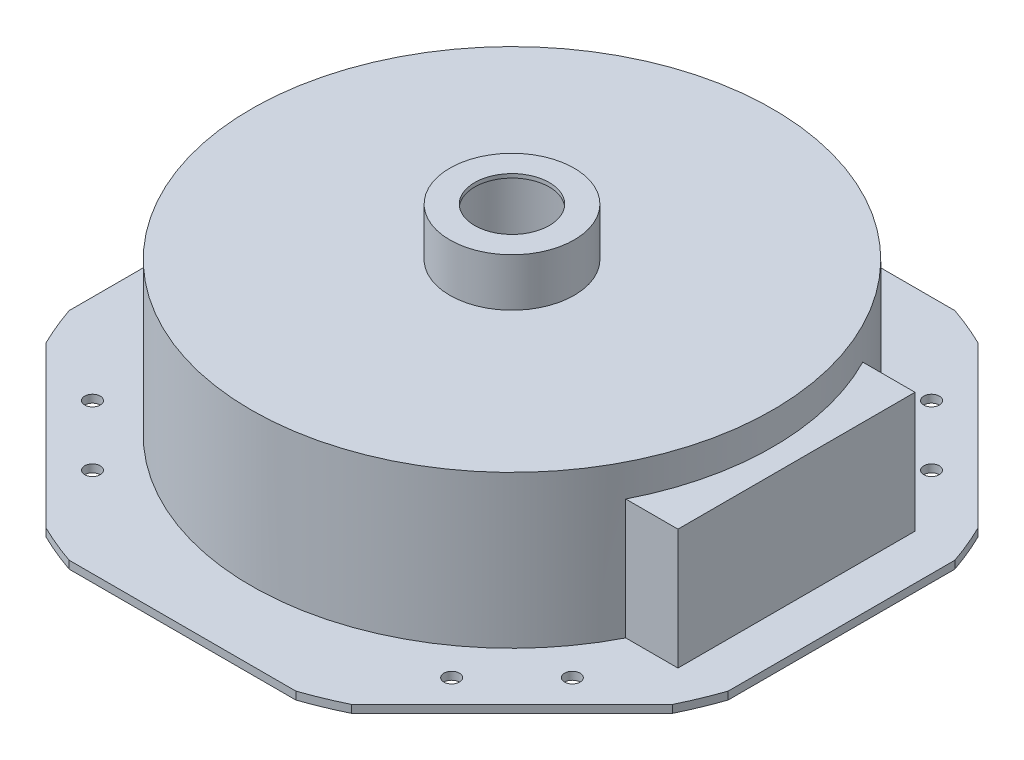
SolidWorks part; units mm, degrees
ref_plane "前视基准面" through (0, 0, 0) normal (0, 0, 1) x (1, 0, 0)
ref_plane "上视基准面" through (0, 0, 0) normal (0, 1, 0) x (1, 0, 0)
ref_plane "右视基准面" through (0, 0, 0) normal (1, 0, 0) x (0, 0, -1)
other "Configuration Table"
sketch "草图1" plane through (0, 0, 0) normal (0, 1, 0) x (1, 0, 0)
  line L1 (-175.6058, 423.95) -> (-423.95, 175.6058)
  line L2 (-423.95, 175.6058) -> (-423.95, -175.6058)
  line L3 (-423.95, -175.6058) -> (-175.6058, -423.95)
  line L4 (-175.6058, -423.95) -> (175.6058, -423.95)
  line L5 (175.6058, -423.95) -> (423.95, -175.6058)
  line L6 (423.95, -175.6058) -> (423.95, 175.6058)
  line L7 (423.95, 175.6058) -> (175.6058, 423.95)
  line L8 (175.6058, 423.95) -> (-175.6058, 423.95)
  circle A0 centre (0, 0) radius 423.95 construction
  circle A1 centre (0, 0) radius 448.35
  dimension "D2" = 896.7
  dimension "D1" = 847.9
extrude "凸台-拉伸1" add sketch "草图1" along normal blind 10 contours L4 A1 L5 L6 L7 L8 L1 L2 L3 region at (0, 0, 0)
sketch "草图2" plane through (0, 10, 0) normal (0, 1, 0) x (1, 0, 0)
  circle A0 centre (0, 0) radius 335.5
  dimension "D1" = 671
extrude "凸台-拉伸2" add sketch "草图2" along normal blind 196 separate body
sketch "草图3" plane through (0, 10, 0) normal (0, 1, 0) x (1, 0, 0)
  line L0 (0, 0) -> (423.95, 0) construction
  line L1 (423.95, -145.8908) -> (423.95, 145.8908) construction
  line L2 (366, 152.5) -> (366, -152.5)
  line L3 (366, 152.5) -> (298.8377, 152.5)
  line L4 (366, -152.5) -> (298.8377, -152.5)
  circle A0 centre (0, 0) radius 335.5 construction
  arc A1 (298.8377, -152.5) -> (298.8377, 152.5) centre (0, 0) ccw
  point P10 (366, 0)
  dimension "D1" = 305
  dimension "D2" = 366
extrude "凸台-拉伸4" add sketch "草图3" along normal blind 154.8 separate body
combine bodies "组合1" operation type add bodies to combine 107 109
shell "抽壳4" thickness 5 removed face at (173.8344, 10, 0)
sketch "草图5" plane through (0, 10, 0) normal (0, -1, 0) x (1, 0, 0)
  line L0 (361, -147.5) -> (295.76, -147.5) construction
  line L1 (361, 147.5) -> (361, -147.5) construction
  line L2 (295.76, 147.5) -> (361, 147.5) construction
  line L3 (361, -147.5) -> (295.76, -147.5) construction
  line L4 (361, 147.5) -> (361, -147.5) construction
  line L5 (295.76, 147.5) -> (361, 147.5) construction
  line L6 (356, -142.5) -> (292.65, -142.5)
  line L7 (356, 142.5) -> (356, -142.5)
  line L8 (292.65, 142.5) -> (356, 142.5)
  circle A0 centre (0, 0) radius 330.5 construction
  arc A1 (295.76, 147.5) -> (295.76, -147.5) centre (0, 0) ccw construction
  arc A2 (292.65, 142.5) -> (292.65, -142.5) centre (0, 0) ccw
  dimension "D1" = 5
extrude "切除-拉伸2" cut sketch "草图5" along normal blind 196
combine bodies "组合2" operation type add bodies to combine 110 112
sketch "草图6" plane through (0, 201, 0) normal (0, -1, 0) x (1, 0, 0)
  circle A0 centre (0, 0) radius 80
  dimension "D1" = 160
extrude "凸台-拉伸6" add sketch "草图6" against normal offset from surface (66.8 mm away) 267.8 up to face at (0, 0, 0)
extrude "凸台-拉伸7" add sketch "草图6<2>" along normal offset from surface (123.6 mm away) 77.4 up to face at (0, 0, 0)
sketch "草图6<2>" plane through (0, 201, 0) normal (0, -1, 0) x (1, 0, 0) same geometry as "草图6"
sketch "草图7" plane through (0, 77.4, 0) normal (0, -1, 0) x (1, 0, 0)
  circle A2 centre (0, 0) radius 75
  circle A3 centre (0, 0) radius 75
  dimension "D1" = 5
extrude "切除-拉伸3" cut sketch "草图7" against normal offset from surface (185.4 mm away) 5 up to face at (0, 267.8, 80)
sketch "草图9" plane through (0, 0, 0) normal (0, -1, 0) x (1, 0, 0)
  line L0 (-231.0613, 308.7016) -> (-308.7016, 231.0613) construction
  line L1 (-402.9383, 196.6176) -> (-196.6176, 402.9383) construction
  line L2 (-269.8814, 269.8814) -> (-299.7779, 299.7779) construction
  circle A0 centre (-308.7016, 231.0613) radius 10
  circle A1 centre (-231.0613, 308.7016) radius 10
  dimension "D1" = 20
  dimension "D2" = 42.28
  dimension "D3" = 109.8
extrude "切除-拉伸11" cut sketch "草图9" against normal blind 25
pattern_circular "阵列(圆周)1" count 4 over 360 about axis through (0, 206, 0) along (0, -1, 0) of "切除-拉伸11" reverse direction yes
sketch "草图10" plane through (0, 0, 0) normal (0, 0, 1) x (1, 0, 0)
  line L0 (-80, 82.4) -> (-335.5, 104.7534)
  line L1 (-80, 201) -> (-80, 77.4) construction
  line L7 (-335.5, 206) -> (-335.5, 10) construction
  line L14 (-80, 77.4) -> (80, 77.4) construction
  dimension "D1" = 5
  dimension "D2" = 85
rib "筋1" sketch "草图10" sketch "草图10" thickness 10 extrusion direction parallel to sketch draft on no parameters "D1"=10
pattern_circular "阵列(圆周)3" count 6 over 360 about axis through (0, -226.2742, 0) along (0, 1, 0) skipping 3 of "筋1"
sketch "草图12" plane through (0, 0, 0) normal (0, 0, 1) x (1, 0, 0)
  line L0 (80, 77.4) -> (80, 201) construction
  line L1 (80, 77.4) -> (80, 201) construction
sketch "草图13" plane through (0, 267.8, 0) normal (0, 1, 0) x (1, 0, 0)
  circle A0 centre (0, 0) radius 48
  dimension "D1" = 96
extrude "切除-拉伸12" cut sketch "草图13" against normal through all
